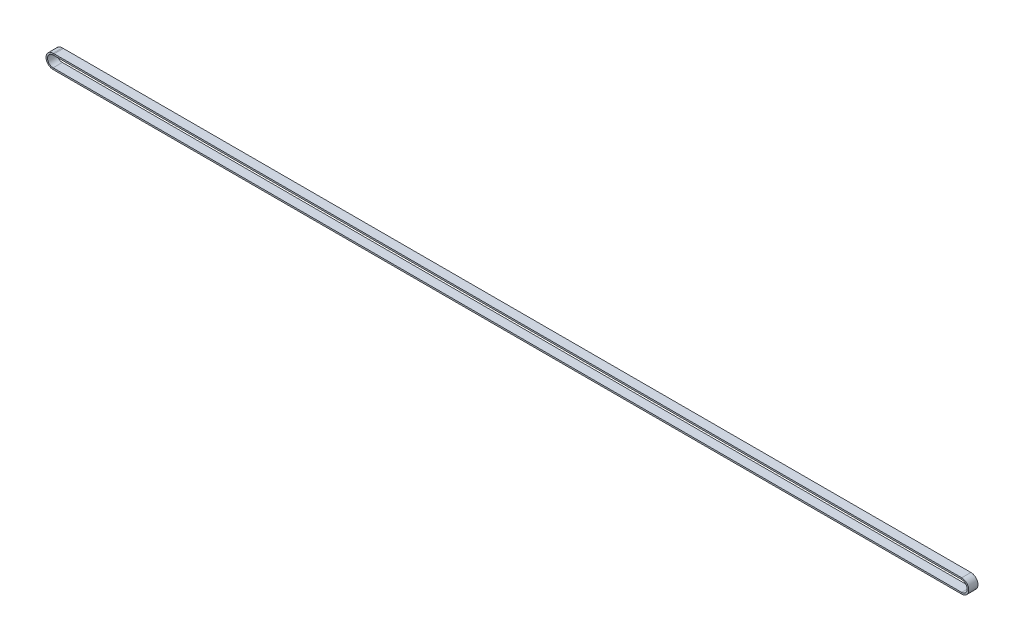
SolidWorks part; units mm, degrees
ref_plane "Front Plane" through (0, 0, 0) normal (0, 0, 1) x (1, 0, 0)
ref_plane "Top Plane" through (0, 0, 0) normal (0, 1, 0) x (1, 0, 0)
ref_plane "Right Plane" through (0, 0, 0) normal (1, 0, 0) x (0, 0, -1)
sketch "Sketch2" plane through (0, 0, -65.4834) normal (0, 0, 1) x (1, 0, 0)
  line L0 (0, 0) -> (1, 0) construction
  line L1 (0, 0) -> (0, 1) construction
  line L2 (-1, -249.662) -> (883.5206, -249.662)
  line L3 (883.5206, -263.462) -> (-1, -263.462)
  arc A0 (-1, -263.462) -> (-1, -249.662) centre (-1, -256.562) cw
  arc A1 (883.5206, -249.662) -> (883.5206, -263.462) centre (883.5206, -256.562) cw
sketch "Sketch3" plane through (0, 0, 0) normal (1, 0, 0) x (0, 0, -1)
  line L1 (65.4834, -251.162) -> (56.4834, -251.162)
  line L2 (65.4834, -251.162) -> (65.4834, -249.662)
  line L3 (65.4834, -249.662) -> (56.4834, -249.662)
  line L4 (56.4834, -251.162) -> (56.4834, -249.662)
  dimension "D1" = 9
  dimension "D2" = 1.5
sweep "Sweep1" add profiles "Sketch3" path "Sketch2"
